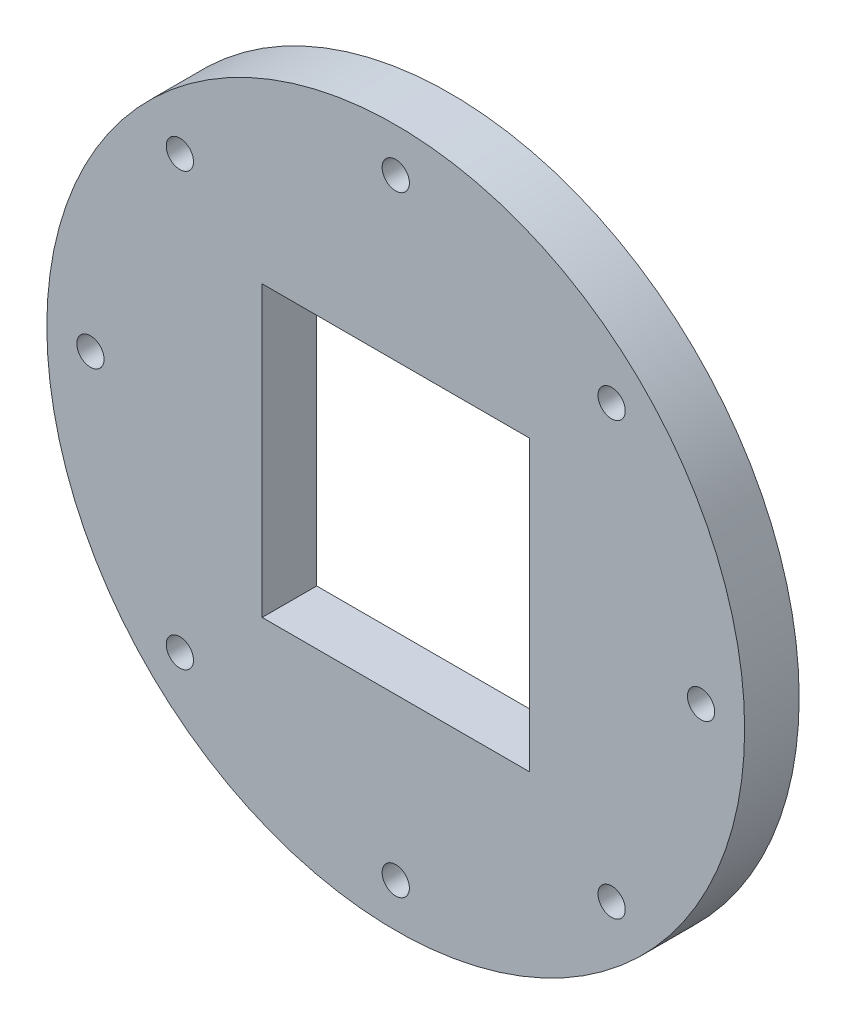
SolidWorks part; units mm, degrees
ref_plane "Alzado" through (0, 0, 0) normal (0, 0, 1) x (1, 0, 0)
ref_plane "Planta" through (0, 0, 0) normal (0, 1, 0) x (1, 0, 0)
ref_plane "Vista lateral" through (0, 0, 0) normal (1, 0, 0) x (0, 0, -1)
sketch "Croquis1" plane through (0, 0, 0) normal (0, 0, 1) x (1, 0, 0)
  circle A0 centre (0, 0) radius 32
  dimension "D1" = 64
extrude "Saliente-Extruir1" add sketch "Croquis1" along normal blind 5
sketch "Croquis2" plane through (0, 0, 5) normal (0, 0, 1) x (1, 0, 0)
  line L0 (0, 0) -> (0, 28) construction
  line L1 (0, 0) -> (19.799, 19.799) construction
  line L2 (0, 0) -> (28, 0) construction
  line L3 (0, 0) -> (19.799, -19.799) construction
  line L4 (0, 0) -> (0, -28) construction
  line L5 (0, 0) -> (-19.799, -19.799) construction
  line L6 (0, 0) -> (-28, 0) construction
  line L7 (0, 0) -> (-19.799, 19.799) construction
  circle A0 centre (0, 28) radius 1.25
  circle A1 centre (0, 0) radius 32 construction
  circle A2 centre (19.799, 19.799) radius 1.25
  circle A3 centre (28, 0) radius 1.25
  circle A4 centre (19.799, -19.799) radius 1.25
  circle A5 centre (0, -28) radius 1.25
  circle A6 centre (-19.799, -19.799) radius 1.25
  circle A7 centre (-28, 0) radius 1.25
  circle A8 centre (-19.799, 19.799) radius 1.25
  point P19 (0, 0)
  dimension "D1" = 2.5
  dimension "D2" = 28
  dimension "D3" = 8
extrude "Cortar-Extruir1" cut sketch "Croquis2" against normal through all
sketch "Croquis3" plane through (0, 0, 5) normal (0, 0, 1) x (1, 0, 0)
  line L0 (0, 32) -> (0, -32) construction
  line L1 (-12.25, -13.25) -> (-12.25, 13.25)
  line L2 (-12.25, -13.25) -> (12.25, -13.25)
  line L3 (12.25, -13.25) -> (12.25, 13.25)
  line L4 (-12.25, 13.25) -> (12.25, 13.25)
  line L5 (-12.25, -13.25) -> (12.25, 13.25) construction
  line L6 (12.25, -13.25) -> (-12.25, 13.25) construction
  circle A0 centre (0, 0) radius 32 construction
  point P0 (0, 0)
  dimension "D1" = 24.5
  dimension "D2" = 26.5
  dimension "D3" = 0
extrude "Cortar-Extruir2" cut sketch "Croquis3" against normal blind 10
